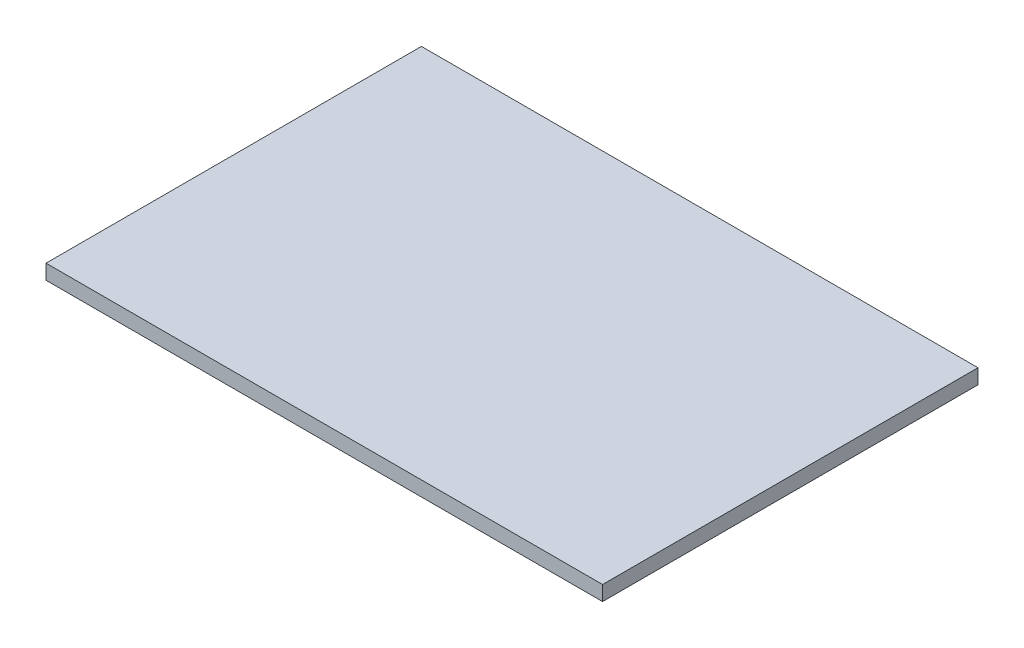
SolidWorks part; units mm, degrees
ref_plane "Front Plane" through (0, 0, 0) normal (0, 0, 1) x (1, 0, 0)
ref_plane "Top Plane" through (0, 0, 0) normal (0, 1, 0) x (1, 0, 0)
ref_plane "Right Plane" through (0, 0, 0) normal (1, 0, 0) x (0, 0, -1)
sketch "Sketch1" plane through (0, 0, 0) normal (0, 1, 0) x (1, 0, 0)
  line L1 (-169, -114) -> (169, -114)
  line L2 (-169, -114) -> (-169, 114)
  line L3 (-169, 114) -> (169, 114)
  line L4 (169, -114) -> (169, 114)
  line L5 (-169, -114) -> (169, 114) construction
  line L6 (-169, 114) -> (169, -114) construction
  point P0 (0, 0)
  dimension "D2" = 228
  dimension "D1" = 338
extrude "Boss-Extrude1" add sketch "Sketch1" along normal blind 9
equation "\"PCLength\"= 320mm'Length across I/O from PS to GPU"
equation "\"PCWidth\"= 242mm'Distance of longest part parallel to GPU(ussually GPU)"
equation "\"PCHeight\"= 172mm'Tallest point with mobo laying flat"
equation "\"WallThickness\"= 9mm'Thickness of each outer tank wall"
equation "\"ThermoBarrierThickness\"= 3mm'Thickness of barrier between hot side and cold side"
equation "\"HotSideGap\"= 35mm'Space in the hot side for a pump"
equation "\"PCClearance\"= 30mm'Clearance from top of tank to top of PC"
equation "\"RadiatorHeight\"= 275mm'Final Height from ground of radiators"
equation "\"D2@Sketch1\"=\"PCHeight\" + \"ThermoBarrierThickness\" + \"HotSideGap\" + (2 * \"WallThickness\")"
equation "\"D1@Boss-Extrude1\"=\"WallThickness\""
